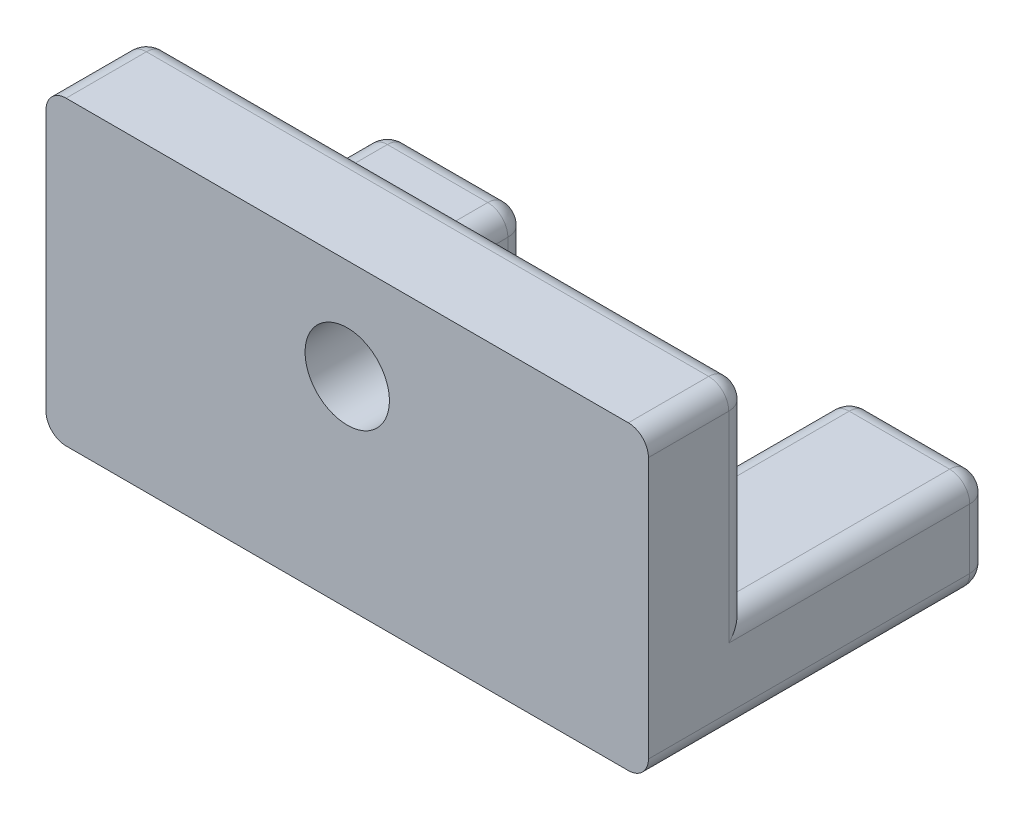
SolidWorks part; units mm, degrees
ref_plane "Ön Düzlem" through (0, 0, 0) normal (0, 0, 1) x (1, 0, 0)
ref_plane "Üst Düzlem" through (0, 0, 0) normal (0, 1, 0) x (1, 0, 0)
ref_plane "Sağ Düzlem" through (0, 0, 0) normal (1, 0, 0) x (0, 0, -1)
sketch "Çizim1" plane through (0, 0, 0) normal (0, 1, 0) x (1, 0, 0)
  line L0 (0, 17) -> (0, 0)
  line L1 (7, 10) -> (23, 10)
  line L2 (0, 0) -> (30, 0)
  line L3 (30, 0) -> (30, 17)
  line L14 (0, 17) -> (7, 17)
  line L15 (7, 17) -> (7, 10)
  line L16 (23, 17) -> (23, 10)
  line L17 (30, 17) -> (23, 17)
  dimension "D3" = 7
  dimension "D7" = 16
  dimension "D8" = 30
  dimension "D2" = 10
  dimension "D4" = 7
  dimension "D5" = 7
  dimension "D6" = 17
  dimension "D17" = 7
extrude "Yükseklik-Ekstrüzyon1" add sketch "Çizim1" along normal blind 5
sketch "Çizim2" plane through (30, 0, 0) normal (1, 0, 0) x (0, 0, -1)
  line L1 (0, 5) -> (5, 5)
  line L2 (0, 5) -> (0, 15)
  line L3 (0, 15) -> (5, 15)
  line L4 (5, 5) -> (5, 15)
  dimension "D1" = 5
  dimension "D2" = 10
extrude "Yükseklik-Ekstrüzyon2" add sketch "Çizim2" against normal blind 30
sketch "Çizim3" plane through (0, 0, -5) normal (0, 0, -1) x (-1, 0, 0)
  line L0 (0, 5) -> (0, 15) construction
  line L1 (0, 15) -> (-30, 15) construction
  circle A0 centre (-15, 10) radius 2.1
  dimension "D2" = 4.2
  dimension "D1" = 15
  dimension "D3" = 5
extrude "Kes-Ekstrüzyon3" cut sketch "Çizim3" against normal blind 5
sketch "Çizim4" plane through (0, 0, -5) normal (0, 0, -1) x (-1, 0, 0)
  circle A0 centre (-15, 10) radius 4.5
  dimension "D1" = 9
extrude "Kes-Ekstrüzyon4" cut sketch "Çizim4" against normal blind 2
fillet "Radyus1" radius 1 23 edges at (23, 5, -13.5) (15, 15, -5) (30, 2.5, -17) (26.5, 5, -17) (23, 2.5, -17) (15, 5, -10) (7, 5, -13.5) (0, 2.5, -17) (7, 2.5, -17) (3.5, 5, -17) (0, 0, -8.5) (3.5, 0, -17) (7, 0, -13.5) (15, 0, -10) (23, 0, -13.5) (26.5, 0, -17) (30, 0, -8.5) (30, 15, -2.5) (0, 15, -2.5)
